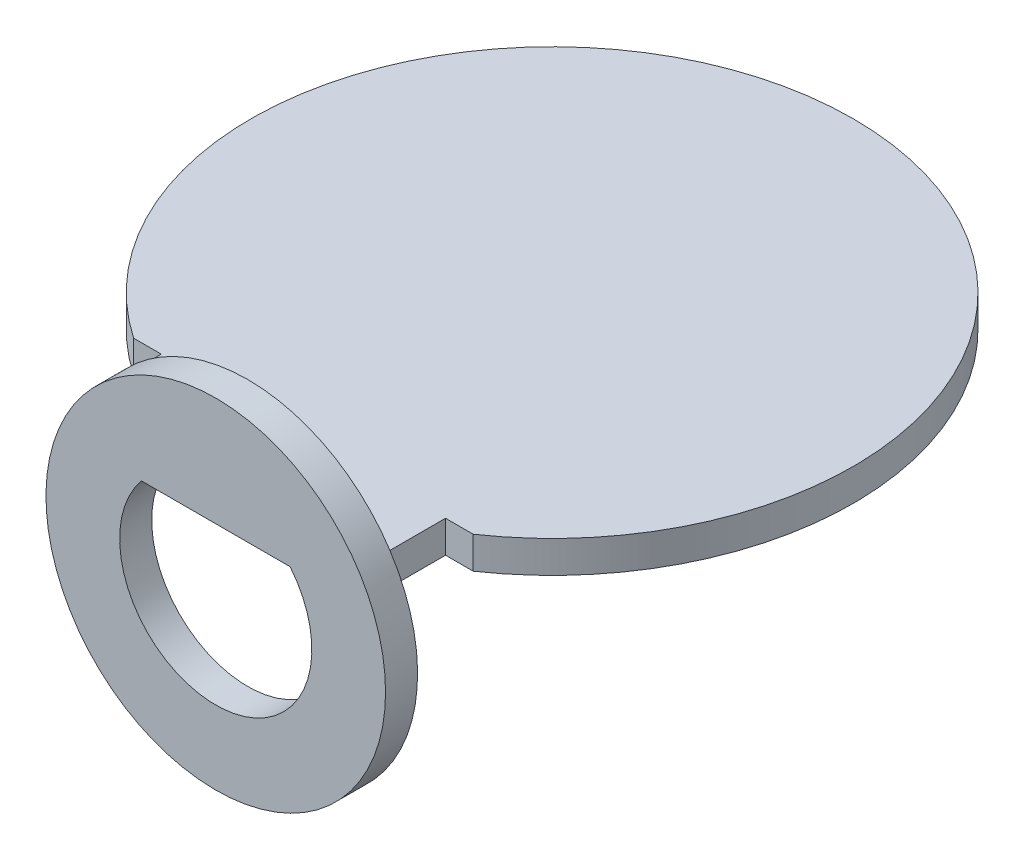
SolidWorks part; units mm, degrees
ref_plane "前视基准面" through (0, 0, 0) normal (0, 0, 1) x (1, 0, 0)
ref_plane "上视基准面" through (0, 0, 0) normal (0, 1, 0) x (1, 0, 0)
ref_plane "右视基准面" through (0, 0, 0) normal (1, 0, 0) x (0, 0, -1)
sketch "草图1" plane through (0, 0, 0) normal (0, 0, 1) x (1, 0, 0)
  line L1 (0, 9.5) -> (-11.6082, 9.5)
  line L2 (0, 9.5) -> (11.6082, 9.5)
  circle A0 centre (0, 0) radius 26.5
  arc A2 (-11.6082, 9.5) -> (11.6082, 9.5) centre (0, 0) ccw
extrude "凸台-拉伸1" add sketch "草图1" along normal blind 5
ref_plane "基准面4" through (0, 9.5, 0) normal (0, -1, 0) x (-1, 0, 0)
sketch "草图2" plane through (0, 9.5, 0) normal (0, -1, 0) x (-1, 0, 0)
  line L0 (-26.5, 0) -> (26.5, 0)
  line L2 (-26.5, 0) -> (-26.5, 8.6831)
  line L3 (26.5, 8.6831) -> (26.5, 0)
  arc A1 (-26.5, 8.6831) -> (26.5, 8.6831) centre (0, 47.5) cw
extrude "凸台-拉伸2" add sketch "草图2" against normal blind 5 contours A1 L3 L0 L2
sketch "草图3" plane through (0, 0, 0) normal (0, 0, 1) x (1, 0, 0)
  line L0 (26.5, 14.5) -> (22.1811, 14.5)
  line L1 (26.5, 14.5) -> (26.5, 9.5)
  line L2 (-51.7, 9.5) -> (51.7, 9.5) construction
  line L3 (26.5, 9.5) -> (22.1811, 9.5)
  line L4 (22.1811, 9.5) -> (22.1811, 14.5)
  line L6 (-22.1811, 9.5) -> (-22.1811, 14.5)
  line L7 (-26.5, 9.5) -> (-22.1811, 9.5)
  line L8 (-26.5, 14.5) -> (-26.5, 9.5)
  line L9 (-26.5, 14.5) -> (-22.1811, 14.5)
extrude "切除-拉伸1" cut sketch "草图3" against normal blind 8.68
